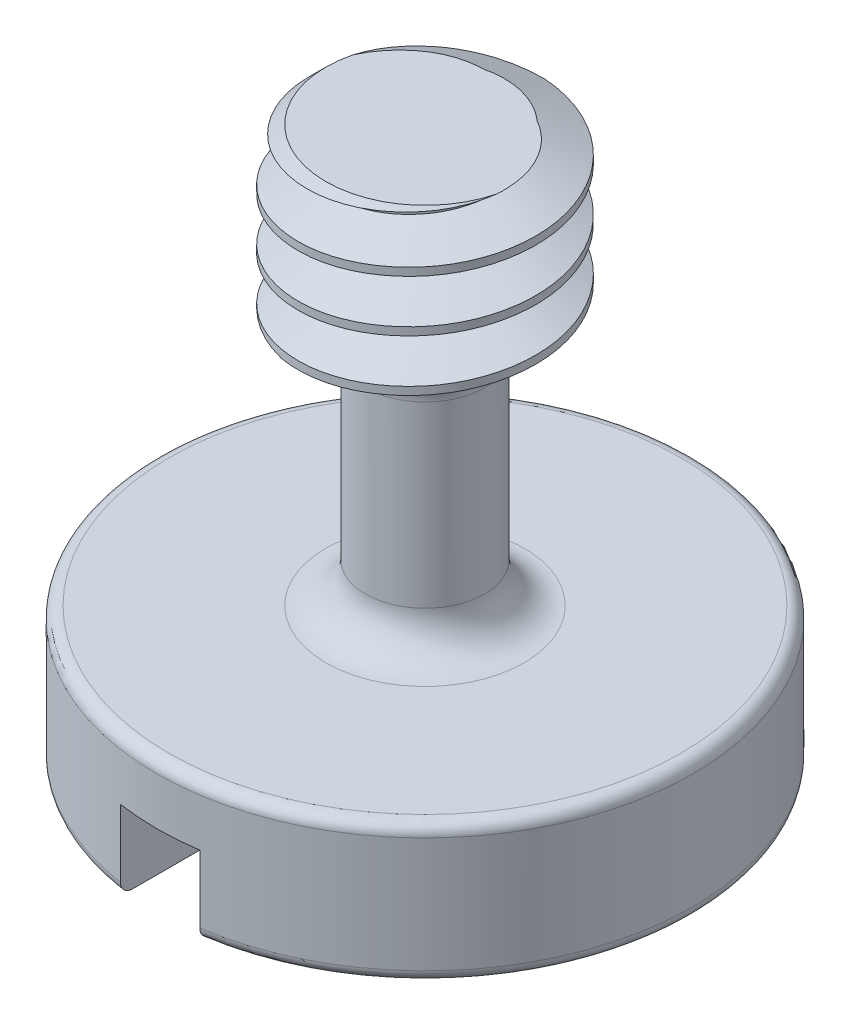
SolidWorks part; units mm, degrees
ref_plane "Front Plane" through (0, 0, 0) normal (0, 0, 1) x (1, 0, 0)
ref_plane "Top Plane" through (0, 0, 0) normal (0, 1, 0) x (1, 0, 0)
ref_plane "Right Plane" through (0, 0, 0) normal (1, 0, 0) x (0, 0, -1)
sketch "Sketch1" plane through (0, 0, 0) normal (0, 0, 1) x (1, 0, 0)
  line L0 (0, 0) -> (6.75, 0)
  line L1 (6.75, 0) -> (6.75, 3.5)
  line L2 (6.75, 3.5) -> (1.5, 3.5)
  line L3 (0, 0) -> (0, 14)
  line L4 (0, 14) -> (3, 14)
  line L5 (3, 14) -> (3, 10)
  line L6 (3, 10) -> (1.5, 10)
  line L7 (1.5, 10) -> (1.5, 3.5)
revolve "Revolve1" add sketch "Sketch1" angle 360 about L3
chamfer "Chamfer1" distance 0.5 angle 45 1 edges at (0, 14, -3)
fillet "Fillet1" radius 1 2 edges at (0, 10, -1.5) (0, 3.5, -1.5)
fillet "Fillet2" radius 0.3 2 edges at (0, 3.5, -6.75) (0, 0, -6.75)
sketch "Sketch2" plane through (0, 0, 0) normal (0, -1, 0) x (1, 0, 0)
  line L0 (0, 6.75) -> (0, -6.75) construction
  line L1 (-1, 6.75) -> (-1, -6.75)
  line L2 (1, 6.75) -> (1, -6.75)
  circle A0 centre (0, 0) radius 6.75 construction
  arc A1 (-1, 6.75) -> (1, 6.75) centre (0, 6.75) cw
  arc A2 (-1, -6.75) -> (1, -6.75) centre (0, -6.75) ccw
  dimension "D1" = 1
  dimension "D2" = 1
extrude "Cut-Extrude1" cut sketch "Sketch2" against normal blind 2
sketch "Sketch3" plane through (0, 14, 0) normal (0, 1, 0) x (-1, 0, 0)
  circle A0 centre (0, 0) radius 3
curve "Helix/Spiral1" pitch 1.3 height 6.175 radius 3 centre (0, 14, 0) axis (0, -1, 0) start towards (0, 0, 1)
sketch3d "3DSketch1"
  line L0 (-3, 14.9243, -0.0117) -> (-3, 13.8243, -0.0117)
  line L1 (-3, 13.8243, -0.0117) -> (-2, 14.2743, -0.0117)
  line L2 (-2, 14.4743, -0.0117) -> (-2, 14.2743, -0.0117)
  line L4 (-3, 14.9243, -0.0117) -> (-2, 14.4743, -0.0117)
  dimension "D2" = 0.2
sweep "Cut-Sweep4" cut profiles "3DSketch1" path "Helix/Spiral1"
